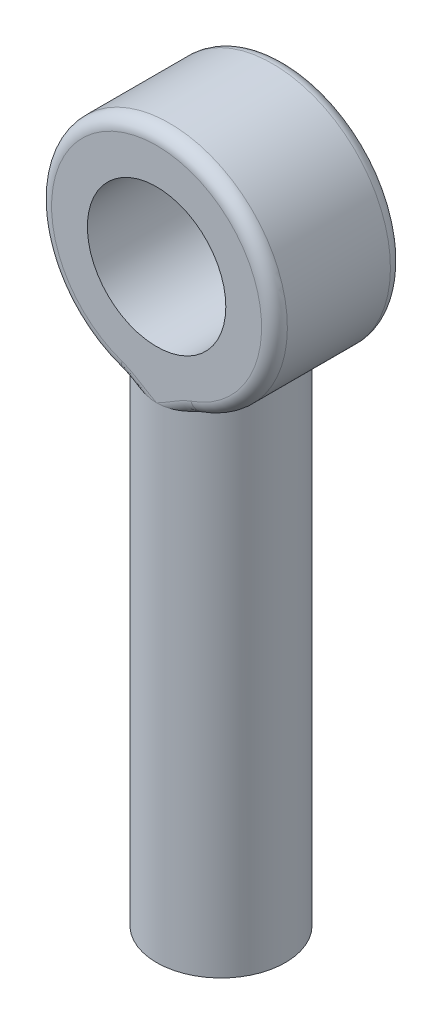
SolidWorks part; units mm, degrees
ref_plane "Front Plane" through (0, 0, 0) normal (0, 0, 1) x (1, 0, 0)
ref_plane "Top Plane" through (0, 0, 0) normal (0, 1, 0) x (1, 0, 0)
ref_plane "Right Plane" through (0, 0, 0) normal (1, 0, 0) x (0, 0, -1)
sketch "Sketch1" plane through (0, 0, 0) normal (0, 1, 0) x (1, 0, 0)
  circle A0 centre (0, 0) radius 1
  dimension "D1" = 2
extrude "Boss-Extrude1" add sketch "Sketch1" along normal blind 8 contours A0
sketch "Sketch2" plane through (0, 0, 0) normal (0, 0, 1) x (1, 0, 0)
  circle A0 centre (0, 9.3574) radius 1.8304
  circle A1 centre (0, 9.3574) radius 1.0747
extrude "Boss-Extrude2" add sketch "Sketch2" along normal mid plane 2
fillet "Fillet1" radius 0.2 2 edges at (1.8304, 9.3574, -1) (1.8304, 9.3574, 1)
